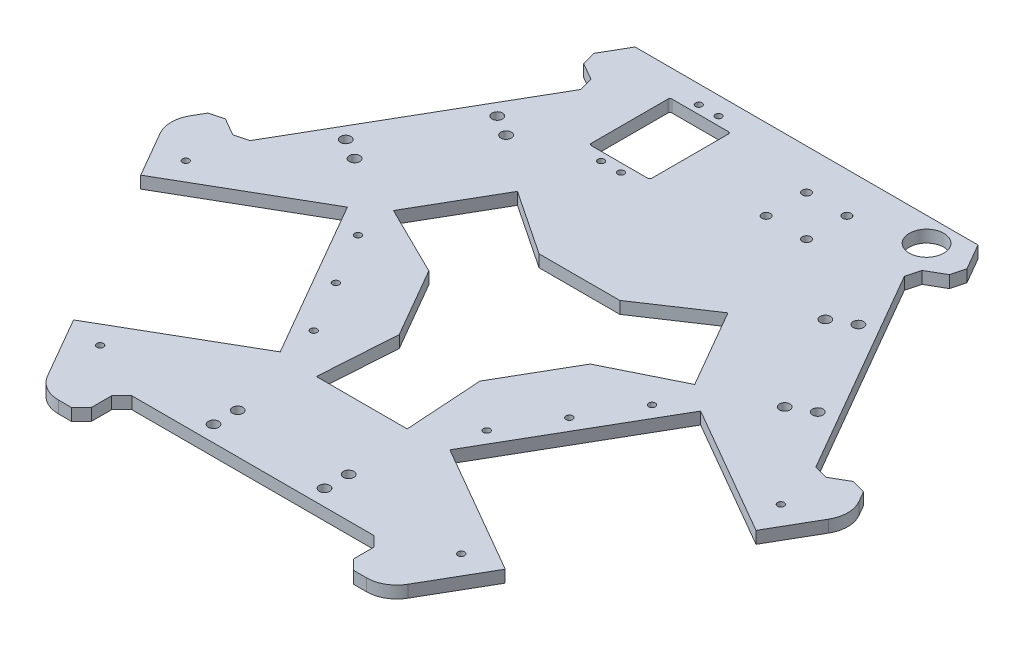
SolidWorks part; units mm, degrees
material "5052-O"
ref_plane "前基準面" through (0, 0, 0) normal (0, 0, 1) x (1, 0, 0)
ref_plane "上基準面" through (0, 0, 0) normal (0, 1, 0) x (1, 0, 0)
ref_plane "右基準面" through (0, 0, 0) normal (1, 0, 0) x (0, 0, -1)
sketch "草圖1" plane through (0, 0, 0) normal (0, 1, 0) x (1, 0, 0)
  line L1 (85, 147.2243) -> (-85, 147.2243)
  line L2 (-85, 147.2243) -> (-170, 0)
  line L3 (-170, 0) -> (-85, -147.2243)
  line L4 (-85, -147.2243) -> (85, -147.2243)
  line L5 (85, -147.2243) -> (170, 0)
  line L6 (170, 0) -> (85, 147.2243)
  circle A0 centre (0, 0) radius 147.2243 construction
  dimension "D1" = 170
extrude "填料-伸長1" add sketch "草圖1" along normal blind 6
ref_axis "基準軸1" through (0, -0.25, 0) along (0, 1, 0)
sketch "草圖46" plane through (0, 6, 0) normal (0, 1, 0) x (1, 0, 0)
  line L0 (-65, -147.2243) -> (65, -147.2243)
  line L1 (-65, -147.2243) -> (-65, -127.2243)
  line L2 (65, -147.2243) -> (65, -127.2243)
  line L3 (-65, -127.2243) -> (65, -127.2243)
  line L4 (-85, -147.2243) -> (85, -147.2243) construction
  point P6 (0, -147.2243)
  point P7 (0, -147.2243)
  dimension "D1" = 20
  dimension "D2" = 130
extrude "除料-伸長31" cut sketch "草圖46" against normal up to next
sketch "草圖8" plane through (0, 6, 0) normal (0, 1, 0) x (1, 0, 0)
  line L0 (65, -127.2243) -> (-65, -127.2243) construction
  line L2 (-27.5, -107.2243) -> (27.5, -107.2243) construction
  line L3 (-27.5, -107.2243) -> (-27.5, -119.2243) construction
  line L4 (-27.5, -119.2243) -> (27.5, -119.2243) construction
  line L5 (27.5, -107.2243) -> (27.5, -119.2243) construction
  circle A0 centre (-27.5, -119.2243) radius 2.6
  circle A1 centre (27.5, -119.2243) radius 2.6
  circle A2 centre (-27.5, -107.2243) radius 2.6
  circle A3 centre (27.5, -107.2243) radius 2.6
  point P7 (0, -119.2243)
  point P14 (0, -127.2243)
  dimension "D3" = 5.2
  dimension "D1" = 55
  dimension "D2" = 12
  dimension "D4" = 8
extrude "除料-伸長6" cut sketch "草圖8" against normal through all
pattern_circular "環狀複製排列1" count 3 over 360 about axis through (0, -0.25, 0) along (0, 1, 0) of "除料-伸長6", "除料-伸長31"
chamfer "導角1" distance 5 angle 45 12 edges at (65, 3, 127.2243) (65, 3, 147.2243) (-65, 3, 147.2243) (-65, 3, 127.2243) (77.6795, 3, -119.9038) (95, 3, -129.9038) (160, 3, -17.3205) (142.6795, 3, -7.3205) (-160, 3, -17.3205) (-142.6795, 3, -7.3205) (-77.6795, 3, -119.9038) (-95, 3, -129.9038)
sketch "草圖5" plane through (0, 6, 0) normal (0, 1, 0) x (1, 0, 0)
  line L0 (-152.5, -30.3109) -> (-107, -109.1192)
  line L1 (-152.5, -30.3109) -> (-87.5481, 7.1891)
  line L2 (-107, -109.1192) -> (-42.0481, -71.6192)
  line L3 (-87.5481, 7.1891) -> (-42.0481, -71.6192)
  line L4 (-170, 0) -> (-85, -147.2243) construction
  dimension "D1" = 75
  dimension "D2" = 91
  dimension "35" = 35
extrude "除料-伸長4" cut sketch "草圖5" against normal through all
sketch "草圖9" plane through (0, 6, 0) normal (0, 1, 0) x (1, 0, 0)
  line L0 (-64.7981, -32.215) -> (-118.4917, -63.215) construction
  line L1 (-42.0481, -71.6192) -> (-87.5481, 7.1891) construction
  line L2 (-118.4917, -63.215) -> (-89.4917, -113.4445) construction
  line L3 (-118.4917, -63.215) -> (-147.4917, -12.9856) construction
  circle A0 centre (-89.4917, -113.4445) radius 1.65
  circle A1 centre (-147.4917, -12.9856) radius 1.65
  dimension "D2" = 3.3
  dimension "D1" = 58
  dimension "D3" = 62
  dimension "D4" = 58
extrude "除料-伸長7" cut sketch "草圖9" against normal through all
mirror "鏡射1" about plane through (0, 0, 0) normal (1, 0, 0) of "除料-伸長4", "除料-伸長7"
fillet "圓角1" radius 15 4 edges at (170, 3, 0) (85, 3, 147.2243) (-170, 3, 0) (-85, 3, 147.2243)
sketch "草圖36" plane through (0, 6, 0) normal (0, 1, 0) x (1, 0, 0)
  line L0 (-72.8699, -2.2343) -> (-57.8699, -28.215) construction
  line L1 (-42.0481, -71.6192) -> (-87.5481, 7.1891) construction
  line L2 (-42.8699, -54.1958) -> (-57.8699, -28.215) construction
  line L3 (-57.8699, -28.215) -> (-64.7981, -32.215) construction
  circle A0 centre (-57.8699, -28.215) radius 1.25
  circle A1 centre (-42.8699, -54.1958) radius 1.25
  circle A2 centre (-72.8699, -2.2343) radius 1.25
  point P7 (-50.3699, -41.2054)
  point P10 (-64.7981, -32.215)
  dimension "D3" = 2.5
  dimension "D1" = 30
  dimension "D2" = 30
  dimension "D4" = 8
hole_wizard "M4x0.7 螺紋孔4" positions "草圖40" profile "草圖41" tap size "M4x0.7" standard "Ansi Metric" end condition through all
sketch "草圖40" plane through (0, 6, 0) normal (0, 1, 0) x (1, 0, 0)
  point P0 (-72.8699, -2.2343)
  point P3 (-57.8699, -28.215)
  point P6 (-42.8699, -54.1958)
sketch "草圖41" plane through (-72.8699, 6, 2.2343) normal (1, 0, 0) x (0, 0, 1)
  line L0 (0, 0) -> (0, 6)
  line L1 (0, 6) -> (1.65, 6)
  line L2 (1.65, 6) -> (1.65, 0)
  line L5 (1.65, 0) -> (0, 0)
  line L11 (0, -6.35) -> (0, 107.95) construction
  dimension "貫穿螺孔鑽直徑" = 3.3
  dimension "貫穿螺孔鑽深度" = 6
cosmetic thread "鑽孔螺紋1" parameters "D1"=10, "D2"=4.3
cosmetic thread "鑽孔螺紋2" parameters "D1"=10, "D2"=4.3
cosmetic thread "鑽孔螺紋3" parameters "D1"=10, "D2"=4.3
mirror "鏡射2" about plane through (0, 0, 0) normal (1, 0, 0) of "M4x0.7 螺紋孔4"
sketch "草圖51" plane through (0, 6, 0) normal (0, 1, 0) x (1, 0, 0)
  line L0 (85, 147.2243) -> (-85, 147.2243) construction
  line L1 (20, 34.641) -> (-20, 34.641)
  line L2 (-20, 34.641) -> (-40, 0)
  line L3 (-40, 0) -> (-20, -34.641)
  line L4 (-20, -34.641) -> (20, -34.641)
  line L5 (20, -34.641) -> (40, 0)
  line L6 (40, 0) -> (20, 34.641)
  circle A0 centre (0, 0) radius 34.641 construction
  dimension "D1" = 40
extrude "除料-伸長35" cut sketch "草圖51" against normal up to next
sketch "草圖52" plane through (0, 6, 0) normal (0, 1, 0) x (1, 0, 0)
  line L0 (-22.5, -73.2243) -> (22.5, -73.2243)
  line L5 (22.5, -73.2243) -> (20, -34.641)
  line L6 (20, -34.641) -> (-20, -34.641)
  line L7 (-20, -34.641) -> (-22.5, -73.2243)
  line L8 (60, -127.2243) -> (-60, -127.2243) construction
  line L9 (-20, 34.641) -> (-52.1641, 56.0977)
  line L10 (-52.1641, 56.0977) -> (-74.6641, 17.1266)
  line L11 (-74.6641, 17.1266) -> (-40, 0)
  line L12 (-40, 0) -> (-20, 34.641)
  line L13 (40, 0) -> (74.6641, 17.1266)
  line L14 (74.6641, 17.1266) -> (52.1641, 56.0977)
  line L15 (52.1641, 56.0977) -> (20, 34.641)
  line L16 (20, 34.641) -> (40, 0)
  line L17 (0, 0) -> (-20, -34.641) construction
  line L18 (0, 0) -> (-20, 34.641) construction
  point P8 (0, -73.2243)
  point P9 (0, -127.2243)
  dimension "D1" = 54
  dimension "D2" = 45
  dimension "D4" = 120
  dimension "D3" = 3
extrude "除料-伸長36" cut sketch "草圖52" against normal up to next
sketch "草圖53" plane through (0, 6, 0) normal (0, 1, 0) x (1, 0, 0)
  line L0 (85, 147.2243) -> (-85, 147.2243) construction
  line L1 (20, 127.2243) -> (40, 127.2243) construction
  line L2 (20, 127.2243) -> (20, 107.2243) construction
  line L3 (20, 107.2243) -> (40, 107.2243) construction
  line L4 (40, 127.2243) -> (40, 107.2243) construction
  line L5 (20, 127.2243) -> (-85, 127.2243) construction
  line L6 (-85, 127.2243) -> (-85, 147.2243) construction
  circle A0 centre (20, 127.2243) radius 2.1
  dimension "D4" = 4.2
  dimension "D1" = 20
  dimension "D2" = 20
  dimension "D3" = 20
  dimension "D5" = 90
  dimension "D6" = 105
extrude "除料-伸長37" cut sketch "草圖53" against normal up to next
pattern_linear "直線複製排列1" count 2 spacing 20 along (1, 0, 0) count 2 spacing 20 along (0, 0, 1) of "除料-伸長37"
sketch "草圖54" plane through (0, 6, 0) normal (0, 1, 0) x (1, 0, 0)
  circle A0 centre (71.5, 135.2243) radius 8.55
  circle A1 centre (40, 127.2243) radius 2.1 construction
  dimension "D1" = 17.1
  dimension "D2" = 31.5
  dimension "D3" = 8
extrude "除料-伸長38" cut sketch "草圖54" against normal up to next
sketch "草圖56" plane through (0, 0, 0) normal (0, -1, 0) x (-1, 0, 0)
  line L0 (-85, 147.2243) -> (85, 147.2243) construction
  line L2 (34.6, 89.8243) -> (34.6, 138.2243) construction
  line L3 (34.6, 138.2243) -> (44.4, 138.2243) construction
  line L4 (44.4, 138.2243) -> (44.4, 89.8243) construction
  circle A0 centre (34.6, 138.2243) radius 1.6
  circle A1 centre (44.4, 138.2243) radius 1.6
  circle A2 centre (44.4, 89.8243) radius 1.6
  circle A3 centre (34.6, 89.8243) radius 1.6
  point P2 (0, 147.2243)
  point P5 (39.5, 138.2243)
  dimension "D1" = 3.2
  dimension "D2" = 9
  dimension "D3" = 39.5
  dimension "D6" = 48.4
  dimension "D7" = 9.8
  dimension "D4" = 2
  dimension "D5" = 2
extrude "除料-伸長40" cut sketch "草圖56" against normal blind 10 contours A3 | A2 | A1 | A0
sketch "草圖55" plane through (0, 6, 0) normal (0, 1, 0) x (1, 0, 0)
  line L1 (-24.5, 134.0243) -> (-54.5, 134.0243)
  line L2 (-24.5, 134.0243) -> (-24.5, 94.0243)
  line L3 (-24.5, 94.0243) -> (-54.5, 94.0243)
  line L4 (-54.5, 134.0243) -> (-54.5, 94.0243)
  line L5 (85, 147.2243) -> (-85, 147.2243) construction
  circle A2 centre (-34.6, 138.2243) radius 1.6 construction
  point P6 (-39.5, 134.0243)
  point P9 (0, 147.2243)
  dimension "D3" = 4.2
  dimension "D1" = 40
  dimension "D2" = 30
  dimension "D4" = 39.5
extrude "除料-伸長39" cut sketch "草圖55" against normal blind 10 contours L2 L1 L4 L3
fillet "圓角2" radius 1 4 edges at (-54.5, 3, -94.0243) (-24.5, 3, -94.0243) (-24.5, 3, -134.0243) (-54.5, 3, -134.0243)
